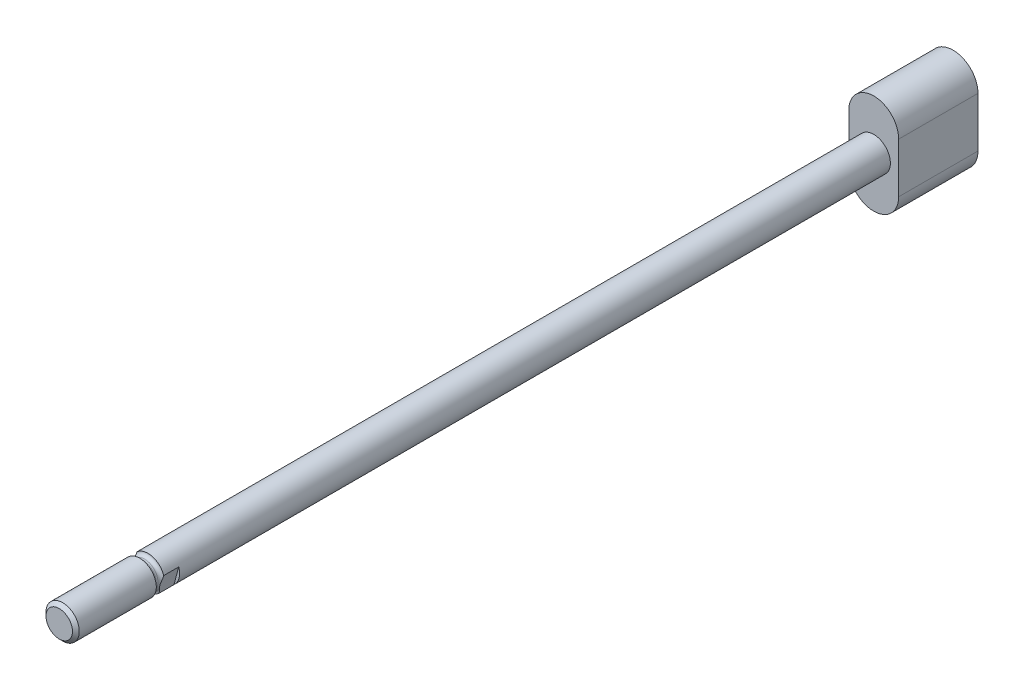
SolidWorks part; units mm, degrees
ref_plane "Front Plane" through (0, 0, 0) normal (0, 0, 1) x (1, 0, 0)
ref_plane "Top Plane" through (0, 0, 0) normal (0, 1, 0) x (1, 0, 0)
ref_plane "Right Plane" through (0, 0, 0) normal (1, 0, 0) x (0, 0, -1)
sketch "Sketch1" plane through (0, 0, 0) normal (1, 0, 0) x (0, 0, -1)
  line L0 (-23, 0) -> (-23, 2.3865)
  line L1 (-23, 2.3865) -> (-22.3865, 3)
  line L2 (-22.3865, 3) -> (-8.5, 3)
  line L3 (-7.9, 2.4) -> (-7.6, 2.4)
  line L4 (-7, 3) -> (-6.5, 3)
  line L5 (-6.5, 3) -> (-6.5, 0)
  line L6 (-6.5, 0) -> (-23, 0)
  line L7 (-6.5, 0) -> (-23, 0) construction
  arc A0 (-8.5, 3) -> (-7.9, 2.4) centre (-7.9, 3) ccw
  arc A1 (-7.6, 2.4) -> (-7, 3) centre (-7.6, 3) ccw
revolve "Revolve1" add sketch "Sketch1" angle 360 about L7
cosmetic thread "Cosmetic Thread1" parameters "D1"=14.5, "D2"=4.773
sketch "Sketch2" plane through (0, 0, 0) normal (1, 0, 0) x (0, 0, -1)
  line L0 (-7, 0) -> (-7, 3)
  line L1 (-7, 3) -> (138.15, 3)
  line L2 (138.15, 3) -> (138.15, 0)
  line L3 (138.15, 0) -> (-7, 0)
  line L4 (138.15, 0) -> (-7, 0) construction
revolve "Revolve2" add sketch "Sketch2" angle 360 about L4
ref_plane "Plane1" through (0, 0, 7) normal (0, 0, 1) x (1, 0, 0)
ref_plane "Plane2" through (0, 0, 4.3) normal (0, 0, 1) x (1, 0, 0)
sketch "Sketch3" plane through (0, 0, 4.3) normal (0, 0, 1) x (1, 0, 0)
  line L0 (-6.4472, -4.7429) -> (3.212, -7.3311)
  line L1 (3.212, -7.3311) -> (5.8002, 2.3281)
  line L2 (5.8002, 2.3281) -> (3.3854, 2.9752)
  line L3 (3.3854, 2.9752) -> (1.1207, -5.4767)
  line L4 (1.1207, -5.4767) -> (-3.7089, -4.1826)
  line L5 (-3.7089, -4.1826) -> (-1.4442, 4.2693)
  line L6 (-1.4442, 4.2693) -> (-3.8591, 4.9163)
  line L7 (-3.8591, 4.9163) -> (-6.4472, -4.7429)
extrude "Cut-Extrude1" cut sketch "Sketch3" along normal blind 3.3
ref_plane "Plane3" through (0, 0, -269) normal (0, 0, 1) x (1, 0, 0)
ref_plane "Plane4" through (0, 0, -138.15) normal (0, 0, 1) x (1, 0, 0)
sketch "Sketch4" plane through (0, 0, -138.15) normal (0, 0, 1) x (1, 0, 0)
  line L0 (4.5, -4.5) -> (4.5, 4.5)
  line L1 (-4.5, 4.5) -> (-4.5, -4.5)
  arc A0 (-4.5, -4.5) -> (0, -9) centre (0, -4.5) ccw
  arc A1 (0, -9) -> (4.5, -4.5) centre (0, -4.5) ccw
  arc A2 (4.5, 4.5) -> (0, 9) centre (0, 4.5) ccw
  arc A3 (0, 9) -> (-4.5, 4.5) centre (0, 4.5) ccw
extrude "Boss-Extrude1" add sketch "Sketch4" along normal blind 14.3
ref_plane "kolben XY" through (0, 0, -138.15) normal (0, 0, 1) x (1, 0, 0)
ref_plane "kolben XZ" through (0, 0, 0) normal (0, -1, 0) x (-1, 0, 0)
ref_plane "kolben YZ" through (0, 0, 0) normal (1, 0, 0) x (0, 0, -1)
ref_axis "kolben X" through (-80.9, 0, -138.15) along (1, 0, 0)
ref_axis "kolben Y" through (0, -50, -138.15) along (0, 1, 0)
ref_axis "kolben Z" through (0, 0, 80.9) along (0, 0, -1)
sketch3d "kolben"
  point P0 (0, 0, -138.15)
